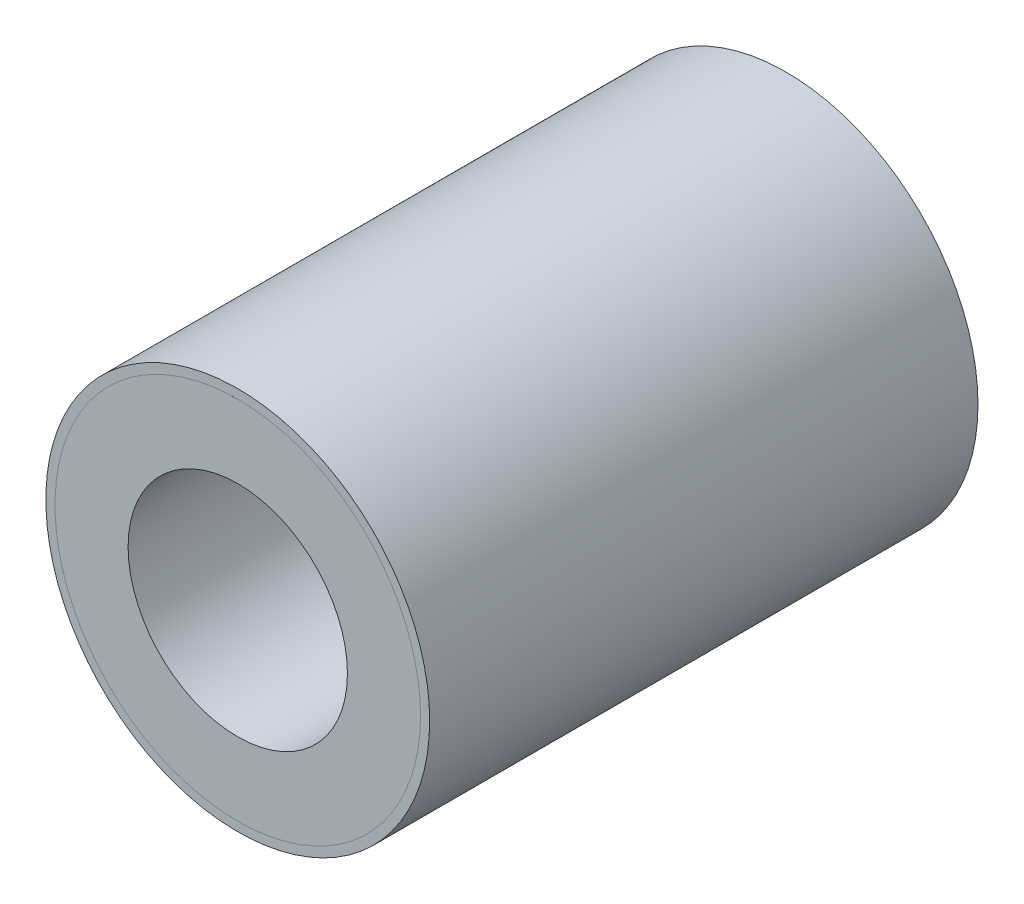
SolidWorks part; units mm, degrees
material "Acier inoxydable chromé"
ref_plane "Front Plane" through (0, 0, 0) normal (0, 0, 1) x (1, 0, 0)
ref_plane "Top Plane" through (0, 0, 0) normal (0, 1, 0) x (1, 0, 0)
ref_plane "Right Plane" through (0, 0, 0) normal (1, 0, 0) x (0, 0, -1)
sketch "Sketch1" plane through (0, 0, 0) normal (0, 0, 1) x (1, 0, 0)
  circle A0 centre (0, 0) radius 6
  circle A1 centre (0, 0) radius 10
  circle A2 centre (0, 0) radius 10.5
  dimension "D1" = 12
  dimension "D2" = 20
  dimension "D3" = 21
extrude "Boss-Extrude1" add sketch "Sketch1" along normal blind 30 contours A1 A0 region at (-9.7172, 0, 0)
extrude "Boss-Extrude2" add sketch "Sketch1<3>" along normal blind 30 separate body contours A2 A1 region at (-10.203, 0, 0)
sketch "Sketch1<3>" plane through (0, 0, 0) normal (0, 0, 1) x (1, 0, 0) same geometry as "Sketch1"
